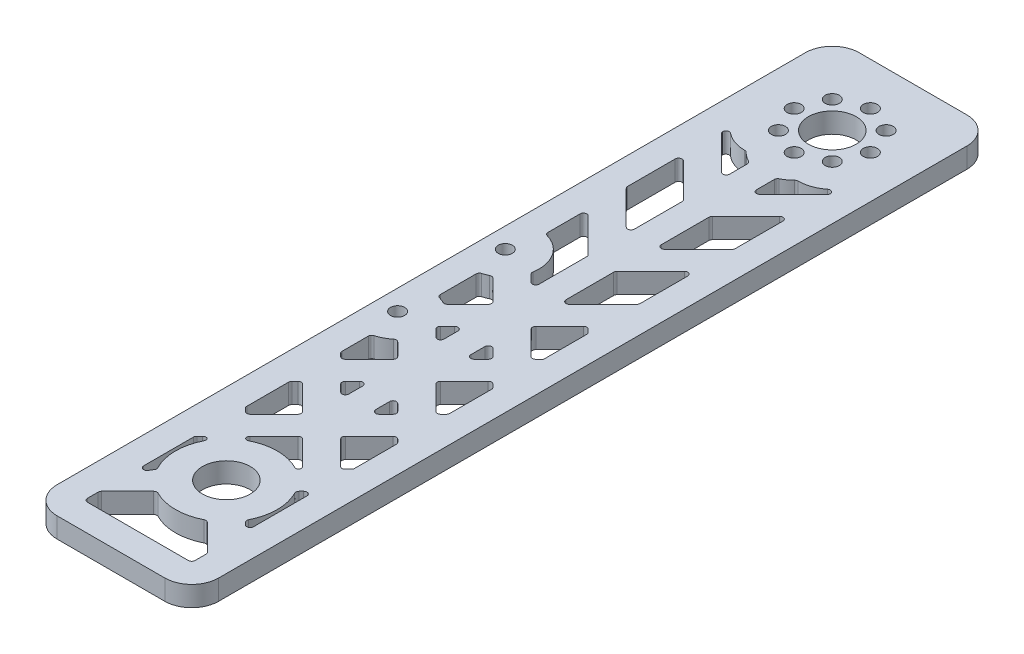
SolidWorks part; units mm, degrees
ref_plane "Front Plane" through (0, 0, 0) normal (0, 0, 1) x (1, 0, 0)
ref_plane "Top Plane" through (0, 0, 0) normal (0, 1, 0) x (1, 0, 0)
ref_plane "Right Plane" through (0, 0, 0) normal (1, 0, 0) x (0, 0, -1)
sketch "Sketch1" plane through (0, 0, 0) normal (0, 1, 0) x (1, 0, 0)
  line L0 (-4.95, -51.0528) -> (4.95, -51.0528) construction
  line L1 (-24, -119.1472) -> (24, -119.1472)
  line L2 (-24, -119.1472) -> (-24, 119.1472)
  line L3 (-24, 119.1472) -> (24, 119.1472)
  line L4 (24, -119.1472) -> (24, 119.1472)
  line L5 (-38.9892, -96.8528) -> (49961.0108, -96.8528) construction
  line L6 (-24, 0) -> (24, 0) construction
  line L7 (-10.6, -96.0528) -> (-2, -96.0528) construction
  line L8 (-10.6, -96.0528) -> (-10.6, -54.0528) construction
  line L9 (-10.6, -54.0528) -> (-2, -54.0528) construction
  line L10 (10.6, -96.0528) -> (10.6, -54.0528) construction
  line L11 (0, -54.0528) -> (0, -96.0528) construction
  line L12 (-10.6, -75.0528) -> (10.6, -75.0528) construction
  line L13 (-4.95, -99.0528) -> (4.95, -99.0528) construction
  line L14 (0, -51.0528) -> (0, -99.0528) construction
  line L15 (-2, -54.0528) -> (-2, -47.5528) construction
  line L16 (-2, -47.5528) -> (2, -47.5528) construction
  line L17 (2, -47.5528) -> (2, -54.0528) construction
  line L18 (2, -54.0528) -> (10.6, -54.0528) construction
  line L19 (2, -102.5528) -> (2, -96.0528) construction
  line L20 (-2, -102.5528) -> (2, -102.5528) construction
  line L21 (-2, -96.0528) -> (-2, -102.5528) construction
  line L22 (2, -96.0528) -> (10.6, -96.0528) construction
  line L23 (4, 0) -> (4, 50000) construction
  line L24 (0, 0) -> (0, 50000) construction
  line L25 (-18, 16) -> (-18, -16) construction
  line L26 (-16, -111.1472) -> (-16, 111.1472) construction
  line L27 (-16, 111.1472) -> (16, 111.1472) construction
  line L28 (16, -111.1472) -> (16, 111.1472) construction
  line L29 (-16, -111.1472) -> (16, -111.1472) construction
  line L30 (0, 0) -> (-35355.3391, 35355.3391) construction
  line L35 (0, 0) -> (35355.3391, 35355.3391) construction
  line L36 (-21.9153, 50.1996) -> (35333.4237, -35305.1395) construction
  line L41 (21.1653, 49.4496) -> (-35334.1737, -35305.8895) construction
  line L42 (-20.2733, 76.8418) -> (35335.0658, -35278.4972) construction
  line L43 (19.4904, 76.0589) -> (-35335.8487, -35279.2801) construction
  line L44 (2.8284, 2.8284) -> (-35352.5106, 35358.1675) construction
  line L45 (-24.7437, 47.3712) -> (35330.5953, -35307.9679) construction
  line L46 (-23.1017, 74.0134) -> (35332.2374, -35281.3257) construction
  line L47 (16.662, 78.8874) -> (-35338.6771, -35276.4517) construction
  line L48 (18.3369, 52.278) -> (-35337.0022, -35303.061) construction
  line L49 (2.8284, -2.8284) -> (35358.1675, 35352.5106) construction
  line L66 (-2.8284, -2.8284) -> (-35358.1675, 35352.5106) construction
  line L67 (-19.0869, 53.028) -> (35336.2522, -35302.311) construction
  line L68 (-17.4449, 79.6702) -> (35337.8942, -35275.6688) construction
  line L69 (22.3188, 73.2305) -> (-35333.0202, -35282.1086) construction
  line L70 (23.9937, 46.6212) -> (-35331.3453, -35308.7179) construction
  line L71 (-2.8284, 2.8284) -> (35352.5106, 35358.1675) construction
  line L72 (-4, 0) -> (-4, 50000) construction
  line L121 (-11.3137, 95.1472) -> (0, 106.4609) construction
  line L122 (8, 87.1472) -> (-8, 87.1472) construction
  line L123 (8, 87.1472) -> (8, 103.1472) construction
  line L124 (8, 103.1472) -> (-8, 103.1472) construction
  line L125 (-8, 87.1472) -> (-8, 103.1472) construction
  line L126 (0, 103.1472) -> (0, 87.1472) construction
  line L127 (8, 95.1472) -> (-8, 95.1472) construction
  line L128 (-11.3137, 95.1472) -> (0, 83.8335) construction
  line L129 (0, 106.4609) -> (11.3137, 95.1472) construction
  line L130 (0, 83.8335) -> (11.3137, 95.1472) construction
  line L131 (5.6569, 100.804) -> (-5.6569, 89.4903) construction
  line L132 (-5.6569, 100.804) -> (5.6569, 89.4903) construction
  line L133 (-16, 38.6274) -> (-4, 26.6274)
  line L144 (-16, 66.9117) -> (-16, 49.9411)
  line L145 (-16, 49.9411) -> (-4, 37.9411)
  line L146 (-4, 37.9411) -> (-4, 54.9117)
  line L147 (-4, 54.9117) -> (-16, 66.9117)
  line L148 (4, 54.9117) -> (16, 66.9117)
  line L149 (16, 66.9117) -> (16, 49.9411)
  line L150 (16, 49.9411) -> (4, 37.9411)
  line L151 (4, 37.9411) -> (4, 54.9117)
  line L153 (-4, 9.6569) -> (-4, 26.6274)
  line L154 (4, 26.6274) -> (16, 38.6274)
  line L155 (16, 38.6274) -> (16, 21.6569)
  line L156 (16, 21.6569) -> (4, 9.6569)
  line L157 (4, 9.6569) -> (4, 26.6274)
  line L158 (-16, 38.6274) -> (-16, 25.9)
  line L159 (-8.1426, 13.7995) -> (-4, 9.6569)
  line L160 (-16, 78.2254) -> (-4, 66.2254)
  line L161 (-4, 66.2254) -> (-4, 74.5593)
  line L162 (-16, 78.2254) -> (-16, 80.982)
  line L163 (4, 74.5593) -> (4, 66.2254)
  line L164 (4, 66.2254) -> (16, 78.2254)
  line L165 (16, 78.2254) -> (16, 80.982)
  line L166 (-12.9247, 7.2678) -> (-5.6569, 0)
  line L167 (-5.6569, 0) -> (-12.9247, -7.2678)
  line L168 (-16, 6.1) -> (-16, -6.1)
  line L169 (70.343, 42.0587) -> (-35284.9961, -35313.2804) construction
  line L170 (-79.597, 51.3127) -> (35275.7421, -35304.0263) construction
  line L171 (77.8112, 21.2427) -> (-35277.5278, -35334.0964) construction
  line L172 (-81.5964, 25.0278) -> (35273.7427, -35330.3112) construction
  line L173 (-82.4254, 48.4843) -> (35272.9136, -35306.8548) construction
  line L174 (-84.4248, 22.1994) -> (35270.9143, -35333.1397) construction
  line L175 (74.9828, 24.0711) -> (-35280.3563, -35331.2679) construction
  line L176 (67.5146, 44.8871) -> (-35287.8245, -35310.4519) construction
  line L177 (-76.7686, 54.1412) -> (35278.5705, -35301.1979) construction
  line L178 (-78.7679, 27.8562) -> (35276.5711, -35327.4828) construction
  line L179 (80.6397, 18.4143) -> (-35274.6994, -35336.9248) construction
  line L180 (73.1714, 39.2303) -> (-35282.1677, -35316.1088) construction
  line L181 (-16, -25.9) -> (-16, -34.9117)
  line L182 (-16, -34.9117) -> (-14.1421, -36.7696)
  line L183 (-14.1421, -36.7696) -> (-5.6569, -28.2843)
  line L184 (-5.6569, -28.2843) -> (-10.8288, -23.1123)
  line L185 (-8.1426, -13.7995) -> (-4, -9.6569)
  line L186 (-4, -9.6569) -> (-4, -18.6274)
  line L187 (-4, -18.6274) -> (-7.9927, -14.6347)
  line L188 (4, -9.6569) -> (4, -18.6274)
  line L189 (4, -18.6274) -> (8.4853, -14.1421)
  line L190 (8.4853, -14.1421) -> (4, -9.6569)
  line L191 (5.6569, 0) -> (14.1421, 8.4853)
  line L192 (14.1421, 8.4853) -> (16, 6.6274)
  line L193 (16, 6.6274) -> (16, -6.6274)
  line L194 (16, -6.6274) -> (14.1421, -8.4853)
  line L195 (14.1421, -8.4853) -> (5.6569, 0)
  line L196 (14.1421, -19.799) -> (16, -21.6569)
  line L197 (16, -21.6569) -> (16, -34.9117)
  line L198 (16, -34.9117) -> (14.1421, -36.7696)
  line L199 (14.1421, -36.7696) -> (5.6569, -28.2843)
  line L200 (5.6569, -28.2843) -> (14.1421, -19.799)
  line L201 (-4, -37.9411) -> (-8.4853, -42.4264)
  line L202 (-8.4853, -42.4264) -> (-4, -46.9117)
  line L203 (-4, -46.9117) -> (-4, -37.9411)
  line L204 (4, -37.9411) -> (4, -46.9117)
  line L205 (4, -46.9117) -> (8.4853, -42.4264)
  line L206 (8.4853, -42.4264) -> (4, -37.9411)
  line L207 (21.011, -63.8418) -> (-35334.328, -35419.1808) construction
  line L208 (25.0443, -109.8971) -> (-35330.2948, 35245.442) construction
  line L209 (18.1826, -61.0134) -> (-35337.1565, -35416.3524) construction
  line L210 (27.8727, -107.0686) -> (-35327.4664, 35248.2704) construction
  line L211 (23.8395, -66.6702) -> (-35331.4996, -35422.0093) construction
  line L212 (22.2158, -112.7255) -> (-35333.1232, 35242.6136) construction
  line L213 (-14.1421, -48.0833) -> (-16, -49.9411)
  line L214 (-16, -49.9411) -> (-16, -63.196)
  line L215 (-16, -63.196) -> (-14.1421, -65.0538)
  line L216 (-14.1421, -65.0538) -> (-5.6569, -56.5685)
  line L217 (-5.6569, -56.5685) -> (-14.1421, -48.0833)
  line L218 (5.6569, -56.5685) -> (14.1421, -48.0833)
  line L219 (14.1421, -48.0833) -> (16, -49.9411)
  line L220 (16, -49.9411) -> (16, -63.196)
  line L221 (16, -63.196) -> (14.1421, -65.0538)
  line L222 (14.1421, -65.0538) -> (5.6569, -56.5685)
  line L223 (0, -62.2254) -> (-8.4853, -70.7107)
  line L224 (-8.4853, -70.7107) -> (-7.4674, -71.7285)
  line L225 (8.4853, -70.7107) -> (7.4674, -71.7285)
  line L226 (0, -62.2254) -> (8.4853, -70.7107)
  line L227 (-14.1421, -76.3675) -> (-16, -78.2254)
  line L228 (-16, -78.2254) -> (-16, -96.8528)
  line L229 (-16, -96.8528) -> (-13.1243, -92.3203)
  line L230 (-16, -106.5097) -> (-16, -111.1472)
  line L231 (-16, -111.1472) -> (16, -111.1472)
  line L232 (16, -111.1472) -> (16, -106.5097)
  line L233 (16, -106.5097) -> (7.4674, -97.9771)
  line L234 (-7.4674, -97.9771) -> (-16, -106.5097)
  line L235 (13.1243, -92.3203) -> (16, -95.196)
  line L236 (16, -95.196) -> (16, -74.5097)
  line L237 (16, -74.5097) -> (13.1243, -77.3854)
  line L238 (-14.1421, -76.3675) -> (-13.1243, -77.3854)
  circle A0 centre (0, 95.1472) radius 7.1
  circle A1 centre (0, -96.8528) radius 7.1 construction
  circle A2 centre (0, -84.8528) radius 7.1
  circle A3 centre (-4.95, -51.0528) radius 2.1 construction
  circle A4 centre (4.95, -51.0528) radius 2.1 construction
  circle A5 centre (-4.95, -99.0528) radius 2.1 construction
  circle A6 centre (4.95, -99.0528) radius 2.1 construction
  circle A7 centre (0, 95.1472) radius 15.1 construction
  circle A8 centre (-8, 103.1472) radius 2.1
  circle A9 centre (8, 103.1472) radius 2.1
  circle A10 centre (8, 87.1472) radius 2.1
  circle A11 centre (-8, 87.1472) radius 2.1
  circle A12 centre (0, 106.4609) radius 2.1
  circle A13 centre (11.3137, 95.1472) radius 2.1
  circle A14 centre (0, 83.8335) radius 2.1
  circle A15 centre (-11.3137, 95.1472) radius 2.1
  circle A16 centre (-8, 87.1472) radius 10.1 construction
  circle A17 centre (8, 87.1472) radius 10.1 construction
  circle A18 centre (0, 83.8335) radius 10.1 construction
  circle A19 centre (-11.3137, 95.1472) radius 10.1 construction
  circle A20 centre (-8, 103.1472) radius 10.1 construction
  circle A21 centre (0, 106.4609) radius 10.1 construction
  circle A22 centre (8, 103.1472) radius 10.1 construction
  circle A23 centre (11.3137, 95.1472) radius 10.1 construction
  circle A24 centre (-18, 16) radius 2.1
  circle A25 centre (-18, -16) radius 2.1
  circle A26 centre (-18, 16) radius 10.1 construction
  circle A27 centre (-18, -16) radius 10.1 construction
  arc A28 (-16, 25.9) -> (-8.1426, 13.7995) centre (-18, 16) cw
  arc A29 (-16, 80.982) -> (-7.492, 77.06) centre (-8, 87.1472) ccw
  arc A30 (-7.492, 77.06) -> (-4, 74.5593) centre (0, 83.8335) ccw
  arc A31 (7.492, 77.06) -> (16, 80.982) centre (8, 87.1472) ccw
  arc A32 (4, 74.5593) -> (7.492, 77.06) centre (0, 83.8335) ccw
  circle A33 centre (0, -84.8528) radius 15.1 construction
  arc A34 (-16, -25.9) -> (-10.8288, -23.1123) centre (-18, -16) ccw
  arc A35 (-16, -6.1) -> (-12.9247, -7.2678) centre (-18, -16) cw
  arc A36 (-8.1426, -13.7995) -> (-7.9927, -14.6347) centre (-18, -16) cw
  arc A37 (-16, 6.1) -> (-12.9247, 7.2678) centre (-18, 16) ccw
  arc A38 (-7.4674, -71.7285) -> (7.4674, -71.7285) centre (0, -84.8528) cw
  arc A39 (-13.1243, -77.3854) -> (-13.1243, -92.3203) centre (0, -84.8528) ccw
  arc A40 (13.1243, -77.3854) -> (13.1243, -92.3203) centre (0, -84.8528) cw
  arc A42 (-7.4674, -97.9771) -> (7.4674, -97.9771) centre (0, -84.8528) ccw
  point P0 (0, 0)
  point P8 (0, -75.0528)
  point P23 (0, -47.5528)
  point P25 (0, -99.0528)
  point P36 (0, 0)
  point P37 (0, -75.0528)
  point P45 (-18, 0)
  point P272 (0, 0)
  point P273 (6.9157, -97.4254)
  point P274 (-6.9094, -97.419)
  point P275 (-6.9093, -97.419)
  point P276 (0, 0)
  dimension "D1" = 14.2
  dimension "D2" = 14.2
  dimension "D7" = 14.2
  dimension "D11" = 4.2
  dimension "D12" = 4.2
  dimension "D13" = 4.2
  dimension "D14" = 4.2
  dimension "D39" = 4.2
  dimension "D24" = 4.2
  dimension "D3" = 48
  dimension "D6" = 24
  dimension "D8" = 12
  dimension "D9" = 21.2
  dimension "D10" = 42
  dimension "D15" = 9.9
  dimension "D16" = 9.9
  dimension "D17" = 48
  dimension "D18" = 14.2
  dimension "D19" = 6.5
  dimension "D20" = 4
  dimension "D21" = 8
  dimension "D32" = 20
  dimension "D33" = 20
  dimension "D34" = 20
  dimension "D37" = 4
  dimension "D38" = 4
  dimension "D36" = 16
  dimension "D40" = 16
  dimension "D23" = 192
  dimension "D25" = 32
  dimension "D26" = 6
  dimension "D29" = 45
  dimension "D30" = 45
  dimension "D31" = 20
  dimension "D42" = 20
  dimension "D43" = 20
  dimension "D44" = 20
  dimension "D45" = 20
  dimension "D50" = 20
  dimension "D22" = 4
  dimension "D27" = 8
  dimension "D28" = 8
  dimension "D35" = 4
  dimension "D41" = 8
  dimension "D46" = 4
  dimension "D47" = 4
  dimension "D48" = 8
  dimension "D51" = 4
  dimension "D52" = 4
extrude "Boss-Extrude1" add sketch "Sketch1" along normal blind 6
fillet "Fillet2" radius 8 4 edges at (24, 3, 119.1472) (-24, 3, 119.1472) (-24, 3, -119.1472) (24, 3, -119.1472)
fillet "Fillet3" radius 1 89 edges at (16, 3, -78.2254) (16, 3, -80.982) (4, 3, -74.5593) (7.492, 3, -77.06) (-16, 3, -80.982) (-16, 3, -78.2254) (-7.492, 3, -77.06) (-4, 3, -74.5593) (-4, 3, -66.2254) (4, 3, -66.2254) (4, 3, -37.9411) (-4, 3, -37.9411) (16, 3, -66.9117) (-16, 3, -49.9411) (4, 3, -54.9117) (-16, 3, -66.9117) (-4, 3, -54.9117) (16, 3, -49.9411) (16, 3, -21.6569) (-16, 3, -38.6274) (16, 3, -38.6274) (-4, 3, -26.6274) (-4, 3, -9.6569) (4, 3, -26.6274) (5.6569, 3, 0) (16, 3, -6.6274) (14.1421, 3, -8.4853) (-16, 3, -6.1) (-12.9247, 3, -7.2678) (-12.9247, 3, 7.2678) (-16, 3, 6.1) (4, 3, -9.6569) (-8.1426, 3, -13.7995) (-16, 3, -25.9) (14.1421, 3, 8.4853) (4, 3, 18.6274) (-5.6569, 3, 0) (8.4853, 3, 14.1421) (4, 3, 9.6569) (-4, 3, 18.6274) (-4, 3, 9.6569) (-8.1426, 3, 13.7995) (-7.9927, 3, 14.6347) (5.6569, 3, 28.2843) (16, 3, 21.6569) (14.1421, 3, 19.799) (16, 3, 34.9117) (14.1421, 3, 36.7696) (-5.6569, 3, 28.2843) (-10.8288, 3, 23.1123) (-16, 3, 25.9) (-16, 3, 34.9117) (-14.1421, 3, 36.7696) (-8.4853, 3, 42.4264) (-4, 3, 37.9411) (-4, 3, 46.9117) (4, 3, 46.9117) (8.4853, 3, 42.4264) (4, 3, 37.9411) (5.6569, 3, 56.5685) (16, 3, 49.9411) (14.1421, 3, 48.0833) (16, 3, 63.196) (14.1421, 3, 65.0538) (-14.1421, 3, 65.0538) (-16, 3, 63.196) (-16, 3, 49.9411) (-14.1421, 3, 48.0833) (-5.6569, 3, 56.5685) (7.4674, 3, 71.7285) (8.4853, 3, 70.7107) (0, 3, 62.2254) (-8.4853, 3, 70.7107) (-7.4674, 3, 71.7285) (-16, 3, 78.2254) (-14.1421, 3, 76.3675) (-13.1243, 3, 77.3854) (-13.1243, 3, 92.3203) (-16, 3, 96.8528) (16, 3, 95.196) (16, 3, 74.5097) (13.1243, 3, 77.3854) (13.1243, 3, 92.3203) (-16, 3, 111.1472) (-16, 3, 106.5097) (-7.4674, 3, 97.9771) (7.4674, 3, 97.9771) (16, 3, 106.5097) (16, 3, 111.1472)
